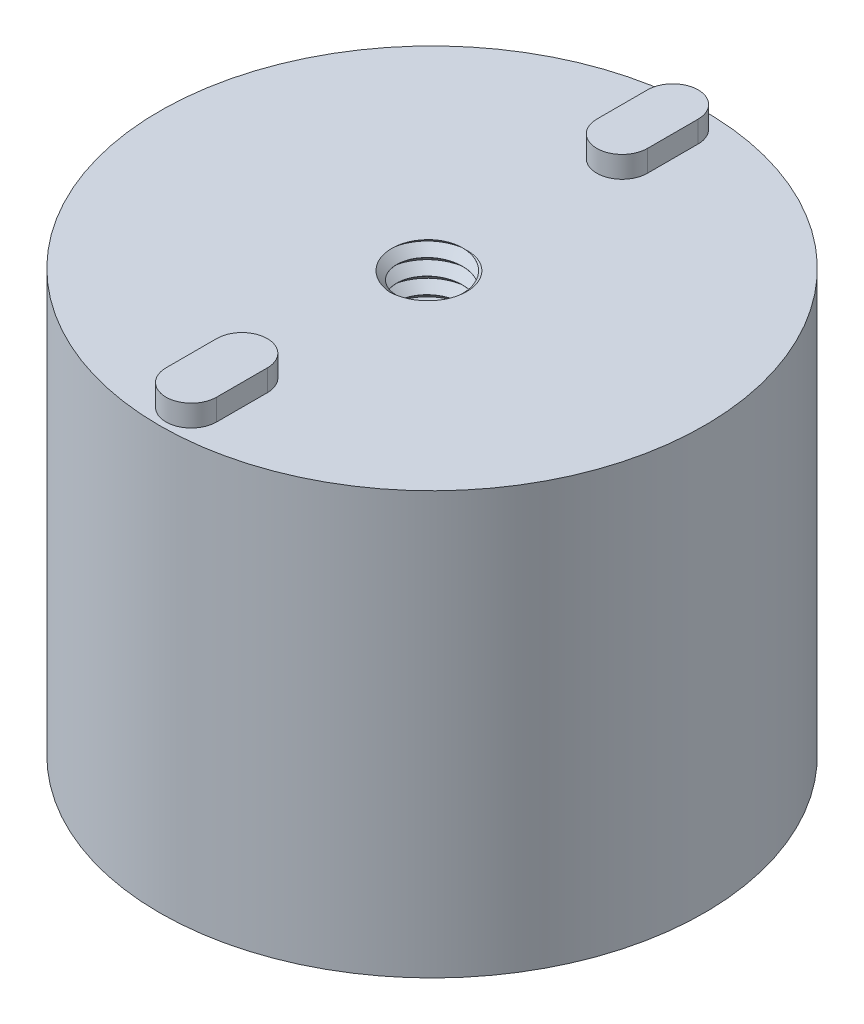
SolidWorks part; units mm, degrees
note: The reader was unsure of these and kept them because the rebuilt part matched: shared geometry of "草图1<2>", "草图3<2>".
ref_plane "前视基准面" through (0, 0, 0) normal (0, 0, 1) x (1, 0, 0)
ref_plane "上视基准面" through (0, 0, 0) normal (0, 1, 0) x (1, 0, 0)
ref_plane "右视基准面" through (0, 0, 0) normal (1, 0, 0) x (0, 0, -1)
sketch "草图1" plane through (0, 0, 0) normal (0, 1, 0) x (1, 0, 0)
  line L0 (0, -16) -> (0, 0) construction
  circle A0 centre (0, 16) radius 1.7
  circle A2 centre (0, -16) radius 1.7
  circle A4 centre (0, 0) radius 21.5
  point P5 (0, 0)
  dimension "D2" = 2
  dimension "D3" = 3.4
  dimension "D4" = 43
  dimension "D1" = 16
extrude "凸台-拉伸1" add sketch "草图1" against normal blind 25
extrude "凸台-拉伸2" add sketch "草图1<2>" along normal blind 10
sketch "草图1<2>" plane through (0, 0, 0) normal (0, 1, 0) x (1, 0, 0) same geometry as "草图1"
sketch "草图2" plane through (0, 10, 0) normal (0, 1, 0) x (1, 0, 0)
  line L0 (0, -15) -> (0, 15) construction
  line L1 (0, 15) -> (0, 19) construction
  line L2 (-2, 15) -> (-2, 19)
  line L3 (0, -19) -> (0, -15) construction
  line L4 (2, 15) -> (2, 19)
  line L10 (-2, -19) -> (-2, -15)
  line L11 (2, -19) -> (2, -15)
  arc A0 (-2, -19) -> (2, -19) centre (0, -19) ccw
  arc A1 (-2, 15) -> (2, 15) centre (0, 15) ccw
  arc A2 (2, 19) -> (-2, 19) centre (0, 19) ccw
  circle A3 centre (0, 0) radius 21.5
  circle A4 centre (0, 0) radius 21.5 construction
  arc A5 (2, -15) -> (-2, -15) centre (0, -15) ccw
  point P4 (0, 17)
  point P18 (0, -17)
  dimension "D1" = 30
  dimension "D3" = 2
  dimension "D4" = 4
  dimension "D5" = 2
  dimension "D2" = 4
extrude "切除-拉伸1" cut sketch "草图2" against normal blind 1.7
sketch "草图3" plane through (0, 8.3, 0) normal (0, 1, 0) x (1, 0, 0)
  circle A0 centre (0, 0) radius 2.6
  dimension "D1" = 5.2
curve "螺旋线/涡状线1" pitch 1.27 height 15.24 turns 12
extrude "切除-拉伸2" cut sketch "草图3<2>" against normal blind 15
sketch "草图3<2>" plane through (0, 8.3, 0) normal (0, 1, 0) x (1, 0, 0) same geometry as "草图3"
sketch "草图4" plane through (0, 0, 0) normal (1, 0, 0) x (0, 0, -1)
  line L0 (-2.6, 8.3) -> (-2.6, 7.67)
  line L1 (-2.6, 7.67) -> (-3.3, 8.3)
  line L3 (-3.3, 8.3) -> (-2.6, 8.93)
  line L4 (-2.6, 8.93) -> (-2.6, 8.3)
  line L5 (-3.3, 8.3) -> (-2.6, 8.3) construction
  dimension "D1" = 0.7
  dimension "D2" = 0.63
sweep "切除-扫描1" cut profiles "草图4" path "螺旋线/涡状线1"
sketch "草图5" plane through (0, -25, 0) normal (0, -1, 0) x (1, 0, 0)
  circle A0 centre (0, 16) radius 1.7
  circle A1 centre (0, 16) radius 1.7 construction
curve "螺旋线/涡状线2" pitch 0.7 height 25.025 turns 35.75
sketch "草图7" plane through (0, 0, 0) normal (1, 0, 0) x (0, 0, -1)
  line L0 (-14.3, -25) -> (-14.3, -24.651)
  line L1 (-14.3, -24.651) -> (-14, -25)
  line L2 (-21.5, -25) -> (21.5, -25) construction
  line L3 (-14, -25) -> (-14.3, -25.349)
  line L4 (-14.3, -25.349) -> (-14.3, -25)
  dimension "D1" = 0.349
  dimension "D2" = 0.3
sweep "切除-扫描2" cut profiles "草图7" path "螺旋线/涡状线2"
pattern_circular "阵列(圆周)2" count 2 over 360 about axis through (0, -25, 0) along (0, 1, 0) of "切除-扫描2"
sketch "草图8" plane through (0, -25, 0) normal (0, -1, 0) x (1, 0, 0)
  circle A0 centre (0, 0) radius 5.1
  dimension "D1" = 10.2
extrude "切除-拉伸3" cut sketch "草图8" against normal blind 10
fillet "圆角1" radius 5 1 edges at (0, -15, -5.1)
